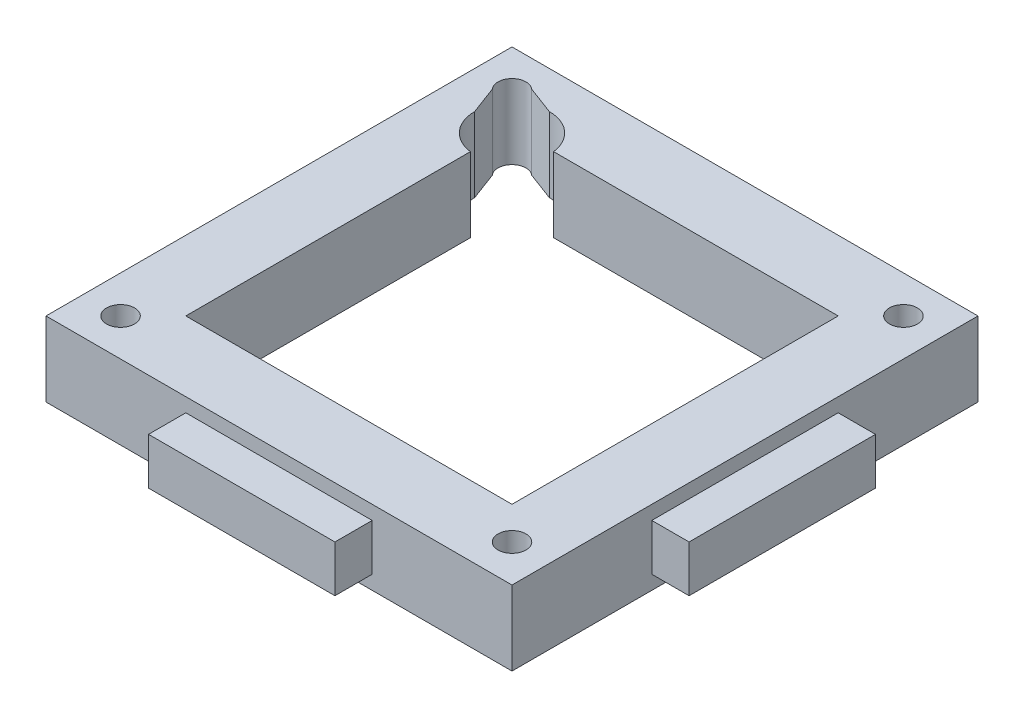
SolidWorks part; units mm, degrees
ref_plane "Front Plane" through (0, 0, 0) normal (0, 0, 1) x (1, 0, 0)
ref_plane "Top Plane" through (0, 0, 0) normal (0, 1, 0) x (1, 0, 0)
ref_plane "Right Plane" through (0, 0, 0) normal (1, 0, 0) x (0, 0, -1)
sketch "Sketch1" plane through (0, 0, 0) normal (0, 1, 0) x (1, 0, 0)
  line L0 (17.5, 17.5) -> (-13.0314, 17.5)
  line L1 (-25, -25) -> (25, -25)
  line L2 (-25, -25) -> (-25, 25)
  line L3 (-25, 25) -> (25, 25)
  line L4 (25, -25) -> (25, 25)
  line L5 (0, 25) -> (0, -25) construction
  line L6 (-25, 0) -> (25, 0) construction
  line L11 (0, 20) -> (0, -20) construction
  line L12 (-20, 0) -> (20, 0) construction
  line L13 (-17.5, -17.5) -> (17.5, -17.5)
  line L16 (17.5, -17.5) -> (17.5, 17.5)
  line L17 (0, 17.5) -> (0, -17.5) construction
  line L18 (-17.5, 0) -> (17.5, 0) construction
  line L19 (-17.5, -17.5) -> (-17.5, 13.0314)
  line L20 (-22.1301, 20.0137) -> (-21, 17)
  line L21 (-20.0137, 22.1301) -> (-17, 21)
  arc A0 (-20.0137, 22.1301) -> (-22.1301, 20.0137) centre (-21, 21) ccw
  circle A1 centre (21, 21) radius 1.5
  circle A2 centre (21, -21) radius 1.5
  circle A3 centre (-21, -21) radius 1.5
  arc A4 (-21, 17) -> (-17, 21) centre (-17, 17) ccw
  point P0 (0, 0)
  point P4 (0, 0)
  point P13 (0, 0)
  dimension "D1" = 50
  dimension "D2" = 50
  dimension "D4" = 35
extrude "Support" add sketch "Sketch1" along normal blind 8 contours L1 L4 L3 L2 A4 L0 L16 L13 L19 L20 A0 L21 A1 A2 A3 region at (-24.2929, 0, 0)
sketch "Sketch2" plane through (0, 0, 0) normal (0, 0, 1) x (1, 0, 0)
  line L4 (-10, 1.5) -> (10, 1.5)
  line L5 (-10, 1.5) -> (-10, 6.5)
  line L6 (-10, 6.5) -> (10, 6.5)
  line L7 (10, 1.5) -> (10, 6.5)
  line L8 (0, 6.5) -> (0, 1.5) construction
  line L9 (-10, 4) -> (10, 4) construction
  point P6 (0, 4)
  dimension "D1" = 20
  dimension "D2" = 5
sketch "Sketch3" plane through (0, 0, 0) normal (1, 0, 0) x (0, 0, -1)
  line L4 (-10, 1.5) -> (10, 1.5)
  line L5 (-10, 1.5) -> (-10, 6.5)
  line L6 (-10, 6.5) -> (10, 6.5)
  line L7 (10, 1.5) -> (10, 6.5)
  line L8 (0, 6.5) -> (0, 1.5) construction
  line L9 (-10, 4) -> (10, 4) construction
  point P6 (0, 4)
  dimension "D1" = 20
  dimension "D2" = 5
extrude "North Cut" cut sketch "Sketch2" along normal blind 4 from surface starting at face at (0, 4, -25)
extrude "South Dowel" add sketch "Sketch2<2>" along normal blind 4 from surface starting at face at (0, 4, 25)
sketch "Sketch2<2>" plane through (0, 0, 0) normal (0, 0, 1) x (1, 0, 0) same geometry as "Sketch2"
extrude "East Dowel" add sketch "Sketch3" along normal blind 4 from surface starting at face at (25, 4, 0)
extrude "West Cut" cut sketch "Sketch3<3>" along normal blind 4 from surface starting at face at (-25, 4, 0)
sketch "Sketch3<3>" plane through (0, 0, 0) normal (1, 0, 0) x (0, 0, -1) same geometry as "Sketch3"
